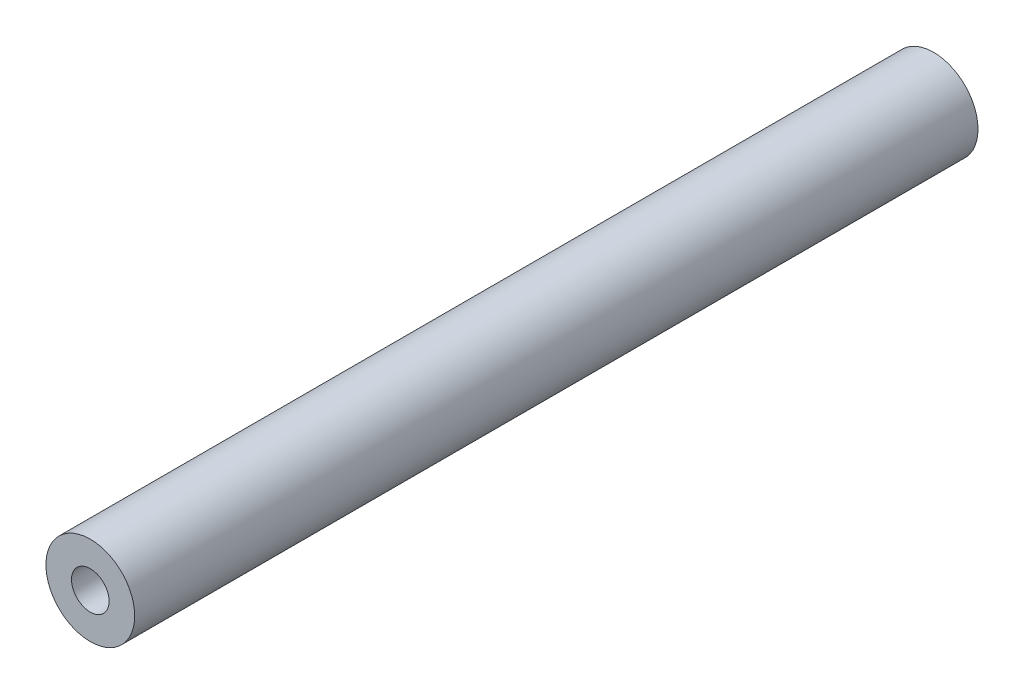
SolidWorks part; units mm, degrees
ref_plane "Front Plane" through (0, 0, 0) normal (0, 0, 1) x (1, 0, 0)
ref_plane "Top Plane" through (0, 0, 0) normal (0, 1, 0) x (1, 0, 0)
ref_plane "Right Plane" through (0, 0, 0) normal (1, 0, 0) x (0, 0, -1)
sketch "Sketch1" plane through (0, 0, 0) normal (0, 0, 1) x (1, 0, 0)
  circle A1 centre (0, 0) radius 4.7625
  dimension "D1" = 9.525
extrude "Boss-Extrude1" add sketch "Sketch1" along normal blind 90.4875
hole_wizard "#10-32 Tapped Hole1" positions "3DSketch1" profile "Sketch2" tap size "#10-32" standard "ANSI Inch" end condition through all
sketch3d "3DSketch1"
  line L0 (0, 0, 90.4875) -> (0, 0, 0) construction
  point P0 (0, 0, 90.4875)
  point P4 (0, 0, 0)
sketch "Sketch2" plane through (0, 0, 90.4875) normal (1, 0, 0) x (0, -1, 0)
  line L0 (0, 0) -> (0, 90.4875)
  line L1 (0, 90.4875) -> (2.0193, 90.4875)
  line L2 (2.0193, 90.4875) -> (2.0193, 0)
  line L5 (2.0193, 0) -> (0, 0)
  line L11 (0, -6.35) -> (0, 107.95) construction
  dimension "Thru Tap Drill Dia." = 4.0386
  dimension "Thru Tap Drill Depth" = 90.4875
cosmetic thread "Hole Thread1" parameters "D2"=4.826
cosmetic thread "Hole Thread2" parameters "D2"=4.826
